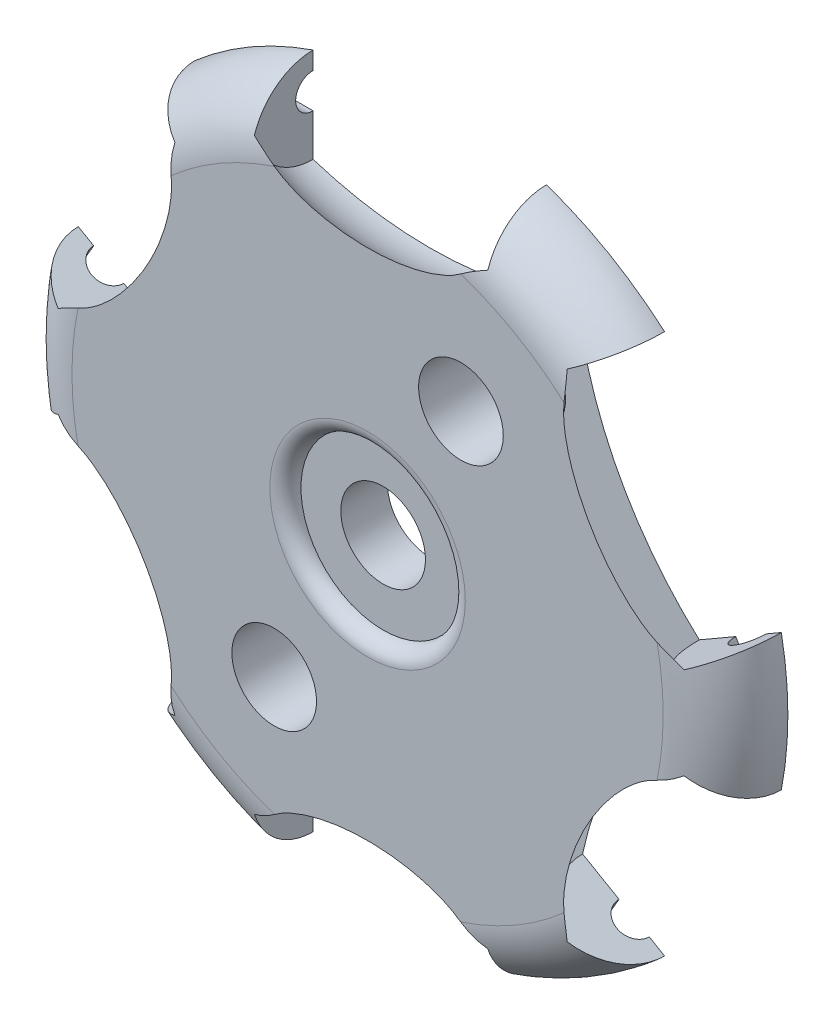
SolidWorks part; units mm, degrees
ref_plane "Front Plane" through (0, 0, 0) normal (0, 0, 1) x (1, 0, 0)
ref_plane "Top Plane" through (0, 0, 0) normal (0, 1, 0) x (1, 0, 0)
ref_plane "Right Plane" through (0, 0, 0) normal (1, 0, 0) x (0, 0, -1)
sketch "Sketch1" plane through (0, 0, 0) normal (0, 0, 1) x (1, 0, 0)
  circle A0 centre (0, 0) radius 18.2626
  dimension "D1" = 36.5252
extrude "Boss-Extrude1" add sketch "Sketch1" along normal blind 3.175
fillet "Fillet1" radius 3.1852 1 edges at (18.2626, 0, 3.175)
sketch "Sketch2" plane through (0, 0, 3.175) normal (0, 0, 1) x (1, 0, 0)
  line L0 (-4.7625, -8.2489) -> (4.7625, 8.2489) construction
  line L1 (0, 0) -> (0, 6.4682) construction
  circle A0 centre (4.7625, 8.2489) radius 2.159
  circle A1 centre (-4.7625, -8.2489) radius 2.159
  circle A4 centre (0, 0) radius 2.159
  point P9 (0, 0)
  dimension "D2" = 4.318
  dimension "D4" = 4.318
  dimension "D1" = 9.525
  dimension "D5" = 30
  dimension "D3" = 2
extrude "Cut-Extrude1" cut sketch "Sketch2" against normal through all
sketch "Sketch5" plane through (0, 0, 0) normal (0, 0, 1) x (1, 0, 0)
  line L0 (-5.9531, 15.4686) -> (5.9531, 15.4686)
  line L1 (5.9531, 15.4686) -> (5.9531, 18.5033)
  line L2 (-5.9531, 15.4686) -> (-5.9531, 18.5033)
  line L3 (-5.9531, 15.4686) -> (-8.5086, 15.4686) construction
  arc A0 (-5.9531, 18.5033) -> (5.9531, 18.5033) centre (0, 0) cw
  circle A1 centre (0, 0) radius 18.2626 construction
  point P5 (0, 15.4686)
  point P9 (0, 19.4373)
  dimension "D1" = 11.9062
  dimension "D2" = 15.4686
  dimension "D3" = 7.9375
revolve "Cut-Revolve1" cut sketch "Sketch5" angle 360 about L3
sketch "Sketch6" plane through (0, 0, 0) normal (1, 0, 0) x (0, 0, -1)
  line L0 (0, -18.2626) -> (0, 17.2651) construction
  circle A0 centre (0, 15.4686) radius 0.889
  arc A1 (-2.9966, 14.9895) -> (0, 12.4339) centre (0, 15.4686) ccw construction
  dimension "D1" = 1.778
extrude "Cut-Extrude2" cut sketch "Sketch6" against normal mid plane 15.875
pattern_circular "CirPattern1" count 6 over 360 about axis through (0, 0, 0) along (0, 0, 1) of "Cut-Revolve1", "Cut-Extrude2"
sketch "Sketch8" plane through (0, 0, 3.175) normal (0, 0, 1) x (1, 0, 0)
  line L1 (0, 5.1326) -> (-4.445, 2.5663)
  line L2 (-4.445, 2.5663) -> (-4.445, -2.5663)
  line L3 (-4.445, -2.5663) -> (0, -5.1326)
  line L4 (0, -5.1326) -> (4.445, -2.5663)
  line L5 (4.445, -2.5663) -> (4.445, 2.5663)
  line L6 (4.445, 2.5663) -> (0, 5.1326)
  circle A0 centre (0, 0) radius 4.445 construction
  dimension "D1" = 8.89
extrude "Cut-Extrude4" [suppressed] cut sketch "Sketch8" against normal blind 1.5875
sketch "Sketch9" plane through (0, 0, 3.175) normal (0, 0, 1) x (1, 0, 0)
  circle A0 centre (0, 0) radius 4.191
  dimension "D1" = 8.382
extrude "Cut-Extrude5" cut sketch "Sketch9" against normal blind 0.7937
fillet "Fillet2" radius 0.7937 1 edges at (4.191, 0, 3.175)
